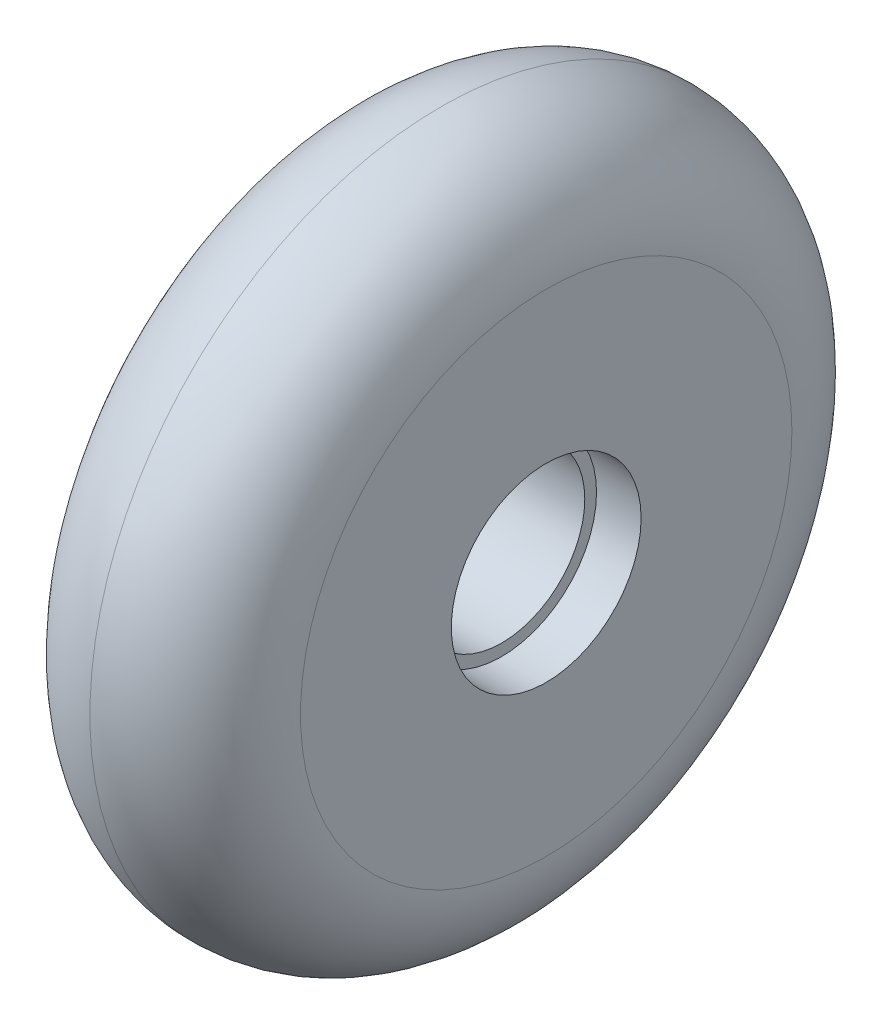
SolidWorks part; units mm, degrees
ref_plane "Front Plane" through (0, 0, 0) normal (0, 0, 1) x (1, 0, 0)
ref_plane "Top Plane" through (0, 0, 0) normal (0, 1, 0) x (1, 0, 0)
ref_plane "Right Plane" through (0, 0, 0) normal (1, 0, 0) x (0, 0, -1)
sketch "Sketch1" plane through (0, 0, 0) normal (1, 0, 0) x (0, 0, -1)
  circle A0 centre (0, 0) radius 40
  circle A1 centre (0, 0) radius 9.475
  dimension "D1" = 80
  dimension "D2" = 18.95
extrude "Boss-Extrude1" add sketch "Sketch1" along normal blind 24
fillet "Fillet1" radius 12 2 edges at (24, 0, -40) (0, 0, -40)
sketch "Sketch2" plane through (24, 0, 0) normal (1, 0, 0) x (0, 0, -1)
  circle A0 centre (0, 0) radius 10.815
  dimension "D1" = 21.63
extrude "Cut-Extrude1" cut sketch "Sketch2" against normal blind 5.08
sketch "Sketch3" plane through (0, 0, 0) normal (-1, 0, 0) x (0, 0, 1)
  circle A0 centre (0, 0) radius 10.815
  dimension "D1" = 21.63
extrude "Cut-Extrude2" cut sketch "Sketch3" against normal blind 5.08
